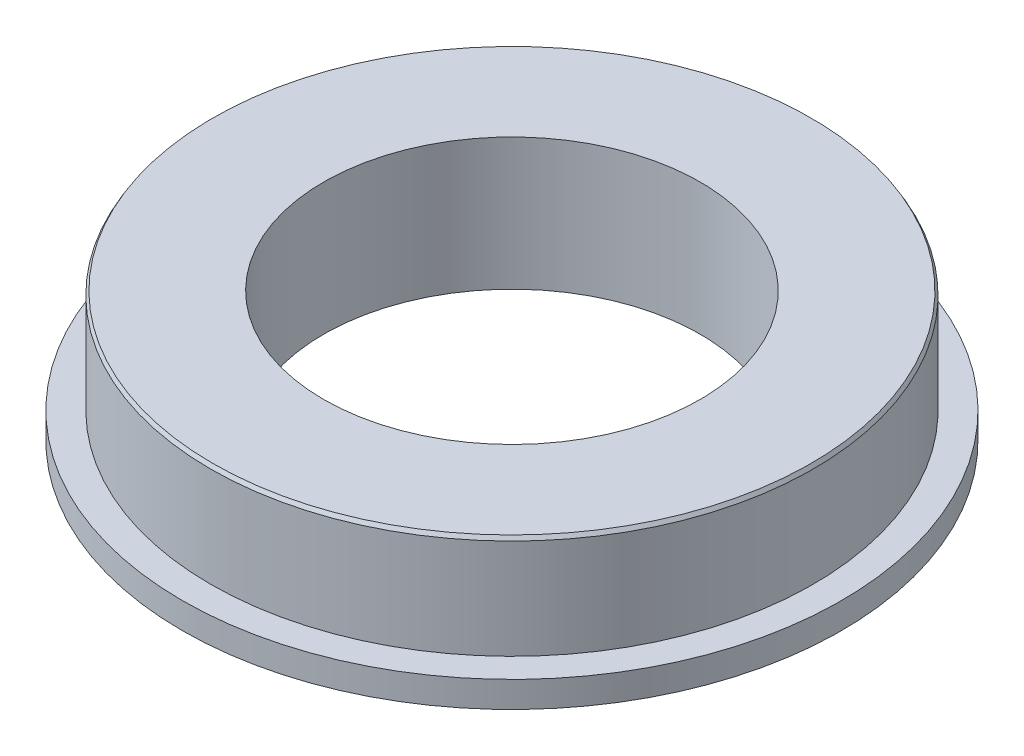
SolidWorks part; units mm, degrees
material "AISI 304"
ref_plane "前视基准面" through (0, 0, 0) normal (0, 0, 1) x (1, 0, 0)
ref_plane "上视基准面" through (0, 0, 0) normal (0, 1, 0) x (1, 0, 0)
ref_plane "右视基准面" through (0, 0, 0) normal (1, 0, 0) x (0, 0, -1)
sketch "草图1" plane through (0, 0, 0) normal (0, 1, 0) x (1, 0, 0)
  circle A0 centre (0, 0) radius 10
  circle A1 centre (0, 0) radius 16
  circle A2 centre (0, 0) radius 17.5
  dimension "d" = 20
  dimension "D " = 32
  dimension "法兰外径" = 35
extrude "凸台-拉伸1" add sketch "草图1" along normal blind 7 contours A1 A0 region at (-15.5475, 0, 0)
extrude "凸台-拉伸2" add sketch "草图1<3>" along normal blind 1.5 contours A2 A1 region at (-17.005, 0, 0)
sketch "草图1<3>" plane through (0, 0, 0) normal (0, 1, 0) x (1, 0, 0) same geometry as "草图1"
chamfer "倒角1" distance 0.2 angle 30 2 edges at (0, 7, 16) (0, 0, 17.5) first distance on face at (0, 1.5, 16) first distance on face at (0, 0, 10)
